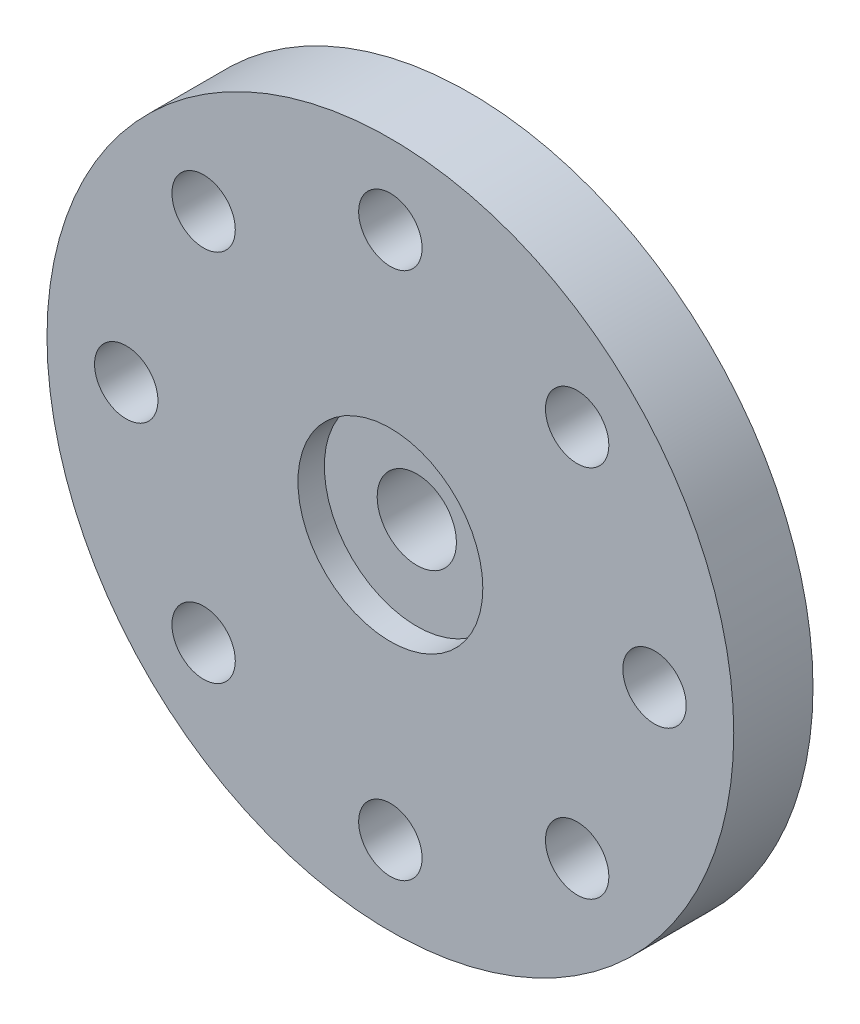
SolidWorks part; units mm, degrees
ref_plane "Front Plane" through (0, 0, 0) normal (0, 0, 1) x (1, 0, 0)
ref_plane "Top Plane" through (0, 0, 0) normal (0, 1, 0) x (1, 0, 0)
ref_plane "Right Plane" through (0, 0, 0) normal (1, 0, 0) x (0, 0, -1)
sketch "Sketch2" plane through (0, 0, 0) normal (0, 0, 1) x (1, 0, 0)
  circle A0 centre (0, 0) radius 13
  circle A1 centre (0, 0) radius 1.5
  dimension "D1" = 26
  dimension "D2" = 3
extrude "Boss-Extrude1" add sketch "Sketch2" along normal blind 3
sketch "Sketch3" plane through (0, 0, 3) normal (0, 0, 1) x (1, 0, 0)
  circle A0 centre (0, 0) radius 3.5
  dimension "D1" = 7
extrude "Cut-Extrude1" cut sketch "Sketch3" against normal blind 1
sketch "Sketch4" plane through (0, 0, 3) normal (0, 0, 1) x (1, 0, 0)
  line L0 (0, 10) -> (0, -10) construction
  line L1 (-10, 0) -> (10, 0) construction
  line L2 (-7.0711, 7.0711) -> (7.0711, -7.0711) construction
  line L3 (-7.0711, -7.0711) -> (7.0711, 7.0711) construction
  circle A0 centre (0, 0) radius 10 construction
  dimension "D1" = 20
  dimension "D2" = 45
  dimension "D3" = 45
sketch "Sketch5" plane through (0, 0, 3) normal (0, 0, 1) x (1, 0, 0)
  circle A0 centre (-7.0711, 7.0711) radius 1.2
  circle A1 centre (0, 10) radius 1.2
  circle A2 centre (7.0711, 7.0711) radius 1.2
  circle A3 centre (10, 0) radius 1.2
  circle A4 centre (7.0711, -7.0711) radius 1.2
  circle A5 centre (0, -10) radius 1.2
  circle A6 centre (-7.0711, -7.0711) radius 1.2
  circle A7 centre (-10, 0) radius 1.2
  dimension "D1" = 2.4
extrude "Cut-Extrude2" cut sketch "Sketch5" against normal through all
sketch "Sketch6" plane through (0, 0, 0) normal (0, 0, -1) x (-1, 0, 0)
  circle A0 centre (0, 0) radius 3
  circle A1 centre (0, 0) radius 1.5
  dimension "D1" = 6
  dimension "D2" = 3
extrude "Boss-Extrude2" add sketch "Sketch6" along normal blind 1
fillet "Fillet1" radius 0.5 2 edges at (-3, 0, -1) (3, 0, 0)
